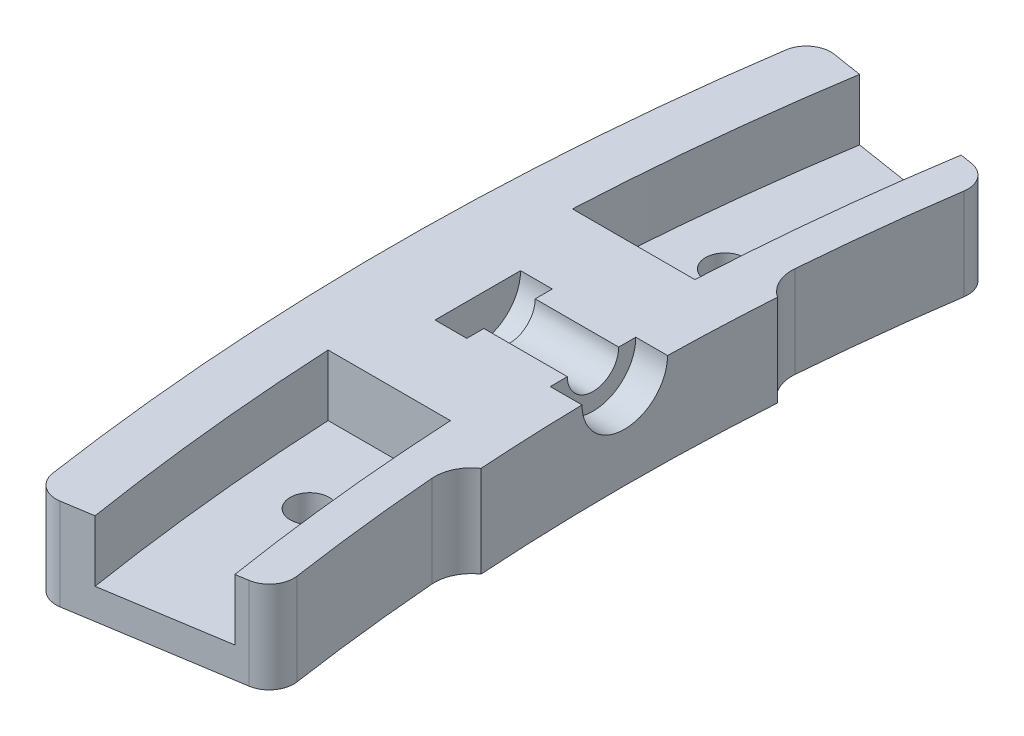
SolidWorks part; units mm, degrees
ref_plane "Front Plane" through (0, 0, 0) normal (0, 0, 1) x (1, 0, 0)
ref_plane "Top Plane" through (0, 0, 0) normal (0, 1, 0) x (1, 0, 0)
ref_plane "Right Plane" through (0, 0, 0) normal (1, 0, 0) x (0, 0, -1)
sketch "Sketch1" plane through (0, 0, 0) normal (0, 1, 0) x (1, 0, 0)
  line L0 (0, 0) -> (-197.5377, -31.2869) construction
  line L1 (0, 0) -> (-197.5377, 31.2869) construction
  line L2 (0, 0) -> (-195, 0) construction
  line L3 (-197.5377, 31.2869) -> (-187.6608, 29.7225)
  line L4 (-187.6608, -29.7225) -> (-197.5377, -31.2869)
  line L5 (0, 0) -> (-201.9823, -31.9908) construction
  line L6 (0, 0) -> (-201.9823, 31.9908) construction
  line L7 (-201.9823, 31.9908) -> (-184.6977, 29.2532)
  line L8 (-201.9823, -31.9908) -> (-184.6977, -29.2532)
  arc A0 (-197.5377, 31.2869) -> (-197.5377, -31.2869) centre (0, 0) ccw
  arc A1 (-187.6608, 29.7225) -> (-187.6608, -29.7225) centre (0, 0) ccw
  arc A2 (-192.5992, -30.5047) -> (-192.5992, 30.5047) centre (0, 0) cw construction
  arc A4 (-184.6977, 29.2532) -> (-184.6977, -29.2532) centre (0, 0) ccw
  arc A5 (-201.9823, 31.9908) -> (-201.9823, -31.9908) centre (0, 0) ccw
  dimension "D1" = 200
  dimension "D2" = 190
  dimension "D3" = 5
  dimension "D5" = 187
  dimension "D6" = 204.5
  dimension "D4" = 18
extrude "Boss-Extrude1" add sketch "Sketch1" along normal blind 10 contours A1 L3 A0 L4 | L7 A5 L8 A0 | A4 L7 A1 L8 region at (-201.4276, 0, 0) region at (-194.2416, 0, 0) region at (-187.7297, 0, 0)
ref_plane "Plane1" through (-195, 0, 0) normal (1, 0, 0) x (0, 0, -1)
sketch "Sketch15" plane through (0, 10, 0) normal (0, 1, 0) x (1, 0, 0)
  line L0 (-187.6608, -29.7225) -> (-197.5377, -31.2869) construction
  line L1 (-185, 10) -> (-205, 10)
  line L2 (-185, 10) -> (-185, -10)
  line L3 (-185, -10) -> (-205, -10)
  line L4 (-205, 10) -> (-205, -10)
  line L5 (-185, 10) -> (-205, -10) construction
  line L6 (-185, -10) -> (-205, 10) construction
  line L7 (-197.5377, 31.2869) -> (-187.6608, 29.7225) construction
  line L8 (-187.6608, -29.7225) -> (-197.5377, -31.2869)
  line L9 (-197.5377, 31.2869) -> (-187.6608, 29.7225)
  arc A2 (-187.6608, 29.7225) -> (-187.6608, -29.7225) centre (0, 0) ccw construction
  arc A3 (-197.5377, 31.2869) -> (-197.5377, -31.2869) centre (0, 0) ccw construction
  arc A4 (-187.6608, 29.7225) -> (-187.6608, -29.7225) centre (0, 0) ccw
  arc A5 (-197.5377, 31.2869) -> (-197.5377, -31.2869) centre (0, 0) ccw
  point P0 (-195, 0)
  line M5 (-201.9823, -31.9908) -> (-184.6977, -29.2532)
  line M7 (-184.6977, 29.2532) -> (-201.9823, 31.9908)
  dimension "D1" = 20
  dimension "D2" = 20
extrude "Cut-Extrude1" cut sketch "Sketch15" against normal blind 5 contours A5 L1 A4 M7 | L3 A5 A4 M5 region at (-193.9153, 10, -20.2762) region at (-193.9153, 10, 20.2762)
ref_plane "Plane2" through (-195, 0, 0) normal (-1, 0, 0) x (0, 0, 1)
sketch "Sketch12" plane through (0, 0, 0) normal (0, 1, 0) x (1, 0, 0)
  line L0 (0, 0) -> (-194.258, -16.9954) construction
  line L1 (0, 0) -> (-193.3317, -25.4526) construction
  line L2 (0, 0) -> (-195, 0) construction
  line L3 (0, 0) -> (-195, 0) construction
  line L4 (0, 0) -> (-194.258, 16.9954) construction
  line L5 (0, 0) -> (-193.3317, 25.4526) construction
  arc A0 (-192.5992, 30.5047) -> (-192.5992, -30.5047) centre (0, 0) ccw construction
  dimension "D1" = 10
  dimension "D2" = 15
hole_wizard "Ø3.2 (3.2) Diameter Hole1" positions "Sketch18" profile "Sketch17" hole size "Ø3.2" standard "ISO" end condition through all
sketch "Sketch18" plane through (0, 0, 0) normal (0, -1, 0) x (-1, 0, 0)
  point P3 (194.258, -16.9954)
  point P6 (194.258, 16.9954)
sketch "Sketch17" plane through (-194.258, 0, 16.9954) normal (1, 0, 0) x (0, 0, -1)
  line L0 (0, 0) -> (0, 10)
  line L1 (0, 10) -> (1.6, 10)
  line L2 (1.6, 10) -> (1.6, 0)
  line L5 (1.6, 0) -> (0, 0)
  line L11 (0, -6.35) -> (0, 107.95) construction
  dimension "Thru Hole Dia." = 3.2
  dimension "Thru Hole Depth" = 10
sketch "Sketch19" plane through (0, 0, 0) normal (0, 1, 0) x (1, 0, 0)
  line L0 (0, 0) -> (-185.1028, -12.1323) construction
  line L1 (0, 0) -> (-185.5, 0) construction
  line L2 (-185.1028, -12.1323) -> (-186.5996, -12.2304)
  line L3 (-185.1028, 12.1323) -> (-186.5996, 12.2304)
  arc A0 (-185.1028, 12.1323) -> (-185.1028, -12.1323) centre (0, 0) ccw
  arc A1 (-184.6977, 29.2532) -> (-184.6977, -29.2532) centre (0, 0) ccw construction
  arc A2 (-186.5996, 12.2304) -> (-186.5996, -12.2304) centre (0, 0) ccw
  dimension "D1" = 185.5
  dimension "D2" = 3.75
extrude "Boss-Extrude2" add sketch "Sketch19" along normal blind 10
fillet "Fillet1" radius 3 2 edges at (-186.5996, 5, -12.2304) (-186.5996, 5, 12.2304)
fillet "Fillet2" radius 2 4 edges at (-201.9823, 5, -31.9908) (-201.9823, 5, 31.9908) (-184.6977, 5, 29.2532) (-184.6977, 5, -29.2532)
sketch "Sketch20" plane through (0, 10, 0) normal (0, 1, 0) x (1, 0, 0)
  line L0 (0, 0) -> (-185, 0) construction
  line L1 (-185, 0) -> (-197.5, 0) construction
  dimension "D1" = 185
  dimension "D2" = 12.5
ref_plane "Plane3" through (-197.5, 0, 0) normal (1, 0, 0) x (0, 0, -1)
sketch "Sketch21" plane through (-197.5, 0, 0) normal (1, 0, 0) x (0, 0, -1)
  line L0 (12.1323, 10) -> (-12.1323, 10) construction
  circle A0 centre (0, 10) radius 2.1
  dimension "D1" = 4.2
extrude "Cut-Extrude2" cut sketch "Sketch21" along normal through all
sketch "Sketch22" plane through (-197.5, 0, 0) normal (1, 0, 0) x (0, 0, -1)
  line L0 (-2.1, 10) -> (2.1, 10) construction
  circle A0 centre (0, 10) radius 3.5
  dimension "D1" = 7
extrude "Cut-Extrude3" cut sketch "Sketch22" along normal blind 2.6
sketch "Sketch23" plane through (-197.5, 0, 0) normal (1, 0, 0) x (0, 0, -1)
  line L0 (-3.5, 10) -> (3.5, 10) construction
  circle A0 centre (0, 10) radius 2.5
  dimension "D1" = 5
extrude "Cut-Extrude4" [suppressed] cut sketch "Sketch23" against normal blind 0.2 and the other way blind 2.7
sketch "Sketch24" [suppressed] plane through (0, 10, 0) normal (0, 1, 0) x (1, 0, 0)
  line L0 (-185.5, 0) -> (-197.5, 0) construction
  line L2 (-197.5, -2.5) -> (-197.5, 2.5) construction
  line L3 (-188.067, 0) -> (-185.467, 0)
  line L4 (-188.067, 0) -> (-188.067, 3.5)
  line L5 (-188.067, 3.5) -> (-185.467, 3.5)
  line L6 (-185.467, 0) -> (-185.467, 3.5)
  arc A0 (-185.4881, 2.1) -> (-185.4881, -2.1) centre (0, 0) ccw construction
  arc A1 (-185.1028, 12.1323) -> (-185.4881, 2.1) centre (0, 0) ccw construction
  dimension "D1" = 2.6
  dimension "D2" = 7
revolve "Cut-Revolve1" [suppressed] cut sketch "Sketch24" angle 360 about L0
sketch "Sketch25" [suppressed] plane through (-188.067, 0, 0) normal (1, 0, 0) x (0, 0, -1)
  line L0 (-2.5, 10) -> (2.5, 10) construction
  circle A0 centre (0, 10) radius 2.5
  dimension "D1" = 5
extrude "Cut-Extrude5" [suppressed] cut sketch "Sketch25" against normal up to surface (9.633 mm away)
sketch "Sketch26" plane through (0, 0, 0) normal (0, -1, 0) x (1, 0, 0)
  line L2 (-199.9971, -31.6764) -> (-186.6626, -29.5645)
  line L3 (-186.6626, 29.5645) -> (-199.9971, 31.6764)
  line L4 (-199.9971, -31.6764) -> (-186.6626, -29.5645)
  line L5 (-186.6626, 29.5645) -> (-199.9971, 31.6764)
  arc A10 (-202.2884, 29.9944) -> (-202.2884, -29.9944) centre (0, 0) ccw
  arc A11 (-202.2884, -29.9944) -> (-199.9971, -31.6764) centre (-200.31, -29.7011) ccw
  arc A12 (-186.6626, -29.5645) -> (-184.9969, -27.2971) centre (-186.9755, -27.5891) ccw
  arc A13 (-186.4092, -14.8532) -> (-184.9969, -27.2971) centre (0, 0) ccw
  arc A14 (-185.1028, -12.1323) -> (-186.4092, -14.8532) centre (-183.4187, -14.6149) ccw
  arc A15 (-185.1028, 12.1323) -> (-185.1028, -12.1323) centre (0, 0) ccw
  arc A16 (-186.4092, 14.8532) -> (-185.1028, 12.1323) centre (-183.4187, 14.6149) ccw
  arc A17 (-184.9969, 27.2971) -> (-186.4092, 14.8532) centre (0, 0) ccw
  arc A18 (-184.9969, 27.2971) -> (-186.6626, 29.5645) centre (-186.9755, 27.5891) ccw
  arc A19 (-199.9971, 31.6764) -> (-202.2884, 29.9944) centre (-200.31, 29.7011) ccw
  arc A20 (-202.2884, 29.9944) -> (-202.2884, -29.9944) centre (0, 0) ccw
  arc A21 (-202.2884, -29.9944) -> (-199.9971, -31.6764) centre (-200.31, -29.7011) ccw
  arc A22 (-186.6626, -29.5645) -> (-184.9969, -27.2971) centre (-186.9755, -27.5891) ccw
  arc A23 (-186.4092, -14.8532) -> (-184.9969, -27.2971) centre (0, 0) ccw
  arc A24 (-185.1028, -12.1323) -> (-186.4092, -14.8532) centre (-183.4187, -14.6149) ccw
  arc A25 (-185.1028, 12.1323) -> (-185.1028, -12.1323) centre (0, 0) ccw
  arc A26 (-186.4092, 14.8532) -> (-185.1028, 12.1323) centre (-183.4187, 14.6149) ccw
  arc A27 (-184.9969, 27.2971) -> (-186.4092, 14.8532) centre (0, 0) ccw
  arc A28 (-184.9969, 27.2971) -> (-186.6626, 29.5645) centre (-186.9755, 27.5891) ccw
  arc A29 (-199.9971, 31.6764) -> (-202.2884, 29.9944) centre (-200.31, 29.7011) ccw
  dimension "D1" = 0
extrude "Cut-Extrude6" cut sketch "Sketch26" against normal blind 2.5
sketch "Sketch27" plane through (0, 10, 0) normal (0, 1, 0) x (1, 0, 0)
  line L0 (-197.5, 0) -> (-185.467, 0) construction
  line L1 (-197.5, -3.5) -> (-197.5, 3.5) construction
  line L3 (-188.067, 3.5) -> (-185.467, 3.5)
  line L4 (-188.067, 3.5) -> (-188.067, 0)
  line L5 (-188.067, 0) -> (-185.467, 0)
  line L6 (-185.467, 3.5) -> (-185.467, 0)
  arc A1 (-185.1028, 12.1323) -> (-185.4881, 2.1) centre (0, 0) ccw construction
  dimension "D1" = 2.6
  dimension "D2" = 7
revolve "Cut-Revolve3" cut sketch "Sketch27" angle 360 about L0
